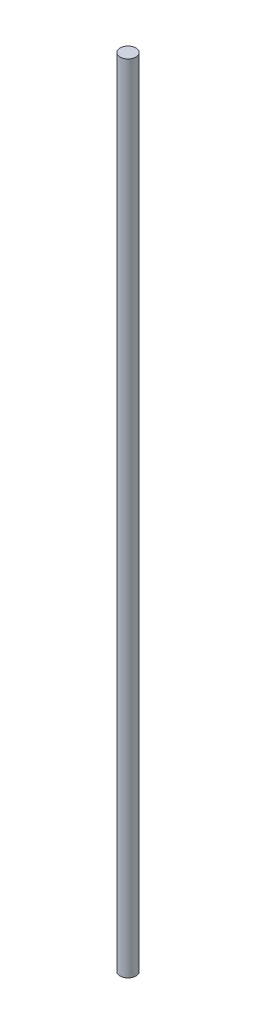
SolidWorks part; units mm, degrees
ref_plane "Front Plane" through (0, 0, 0) normal (0, 0, 1) x (1, 0, 0)
ref_plane "Top Plane" through (0, 0, 0) normal (0, 1, 0) x (1, 0, 0)
ref_plane "Right Plane" through (0, 0, 0) normal (1, 0, 0) x (0, 0, -1)
sketch "Sketch1" plane through (0, 0, 0) normal (0, 1, 0) x (1, 0, 0)
  circle A0 centre (0, 0) radius 0.5
  dimension "D1" = 1
extrude "Boss-Extrude1" add sketch "Sketch1" along normal blind 50
